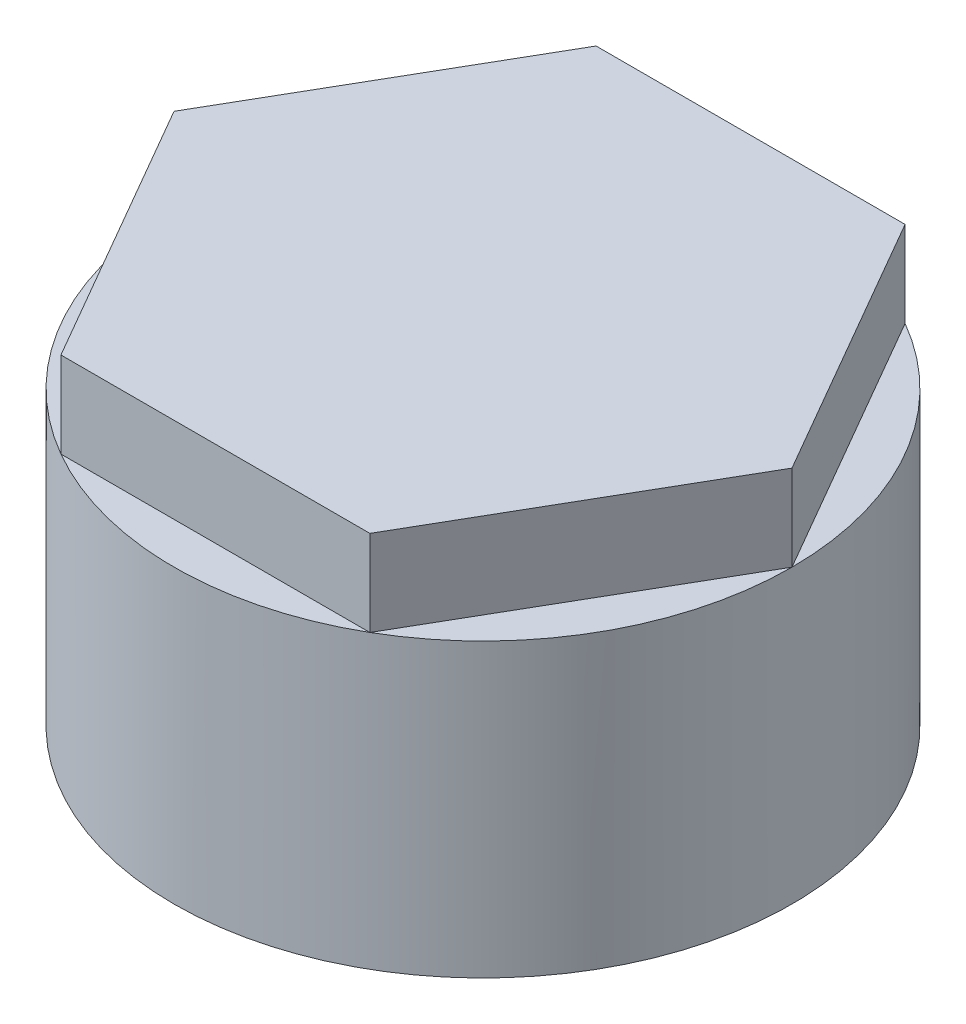
SolidWorks part; units mm, degrees
material "AISI 1035 Acciaio (SS)"
ref_plane "Piano frontale" through (0, 0, 0) normal (0, 0, 1) x (1, 0, 0)
ref_plane "Piano superiore" through (0, 0, 0) normal (0, 1, 0) x (1, 0, 0)
ref_plane "Piano destro" through (0, 0, 0) normal (1, 0, 0) x (0, 0, -1)
sketch "Schizzo1" plane through (0, 0, 0) normal (0, 0, 1) x (1, 0, 0)
  line L0 (-15, 0) -> (-15, 16)
  line L1 (-15, 16) -> (0, 16)
  line L2 (0, 16) -> (0, 22)
  line L3 (0, 22) -> (-18, 22)
  line L4 (-18, 22) -> (-18, 0)
  line L5 (-18, 0) -> (-15, 0)
  line L6 (0, 0) -> (0, 29.0615) construction
  dimension "D1" = 36
  dimension "D2" = 30
  dimension "D3" = 22
  dimension "D4" = 16
revolve "Rivoluzione1" add sketch "Schizzo1" angle 360 about L6
sketch "Schizzo2" plane through (0, 22, 0) normal (0, 1, 0) x (1, 0, 0)
  line L0 (-9, 15.5885) -> (9, 15.5885)
  line L1 (9, 15.5885) -> (18, 0)
  line L2 (18, 0) -> (9, -15.5885)
  line L3 (9, -15.5885) -> (-9, -15.5885)
  line L4 (-9, -15.5885) -> (-18, 0)
  line L5 (-18, 0) -> (-9, 15.5885)
  circle A0 centre (0, 0) radius 18
  circle A1 centre (0, 0) radius 18 construction
  circle M8 centre (0, 0) radius 18
extrude "Taglio-Estrusione1" cut sketch "Schizzo2" against normal blind 5 contours L5 M8 | L4 M8 | L3 M8 | L2 M8 | L1 M8 | L0 M8 region at (0, 22, -16.5588) region at (-14.3404, 22, -8.2794) region at (14.3404, 22, -8.2794) region at (-14.3404, 22, 8.2794) region at (14.3404, 22, 8.2794) region at (0, 22, 16.5588)
